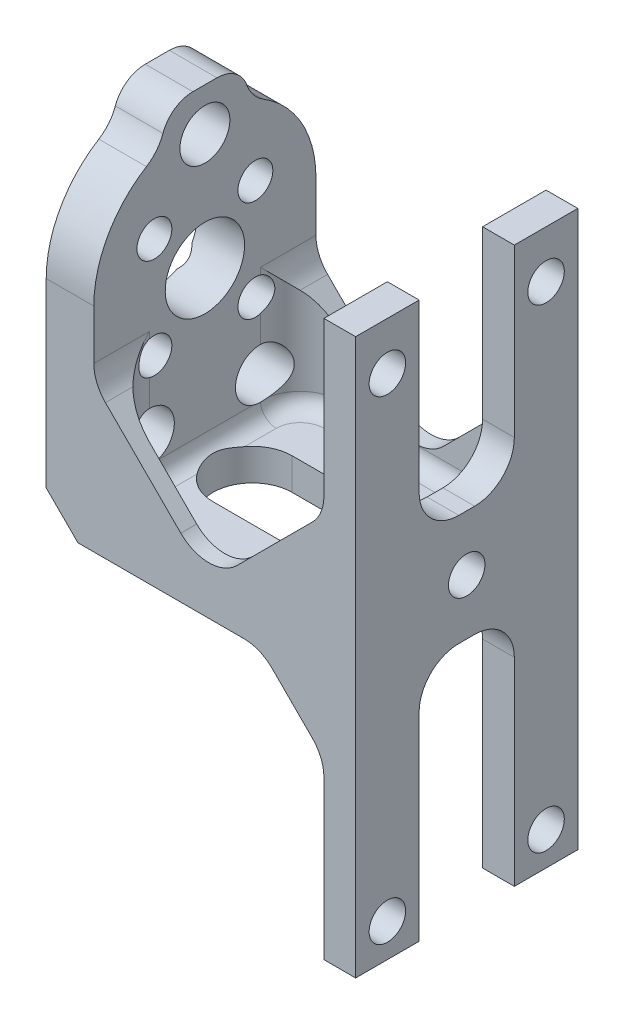
SolidWorks part; units mm, degrees
ref_plane "Front Plane" through (0, 0, 0) normal (0, 0, 1) x (1, 0, 0)
ref_plane "Top Plane" through (0, 0, 0) normal (0, 1, 0) x (1, 0, 0)
ref_plane "Right Plane" through (0, 0, 0) normal (1, 0, 0) x (0, 0, -1)
sketch "Sketch1" plane through (0, 0, 0) normal (0, 1, 0) x (1, 0, 0)
  line L0 (-7.25, 7) -> (7.25, -7) construction
  line L1 (-7.25, 7) -> (7.25, 7)
  line L2 (-7.25, 7) -> (-7.25, -7)
  line L3 (-7.25, -7) -> (7.25, -7)
  line L4 (7.25, 7) -> (7.25, -7)
  dimension "D2" = 14.5
  dimension "D1" = 14
extrude "base" add sketch "Sketch1" along normal blind 2
sketch "Sketch3" plane through (0, 0, 7) normal (0, 0, 1) x (1, 0, 0)
  line L0 (-7.25, 2) -> (7.25, 2) construction
  line L1 (-7.25, 0) -> (-10.25, 0)
  line L2 (-7.25, 0) -> (-7.25, 19)
  line L3 (-7.25, 19) -> (-10.25, 19)
  line L4 (-10.25, 0) -> (-10.25, 19)
  dimension "D1" = 3
  dimension "D2" = 17
extrude "motorFlange" add sketch "Sketch3" against normal up to surface (14 mm away) up to face at (0, 1, -7)
hole_wizard "CSK for M2 Flat Head Machine Screw1" positions "Sketch6" profile "Sketch7" countersink size "M2" standard "ANSI Metric"
sketch "Sketch6" plane through (-10.25, 0, 0) normal (-1, 0, 0) x (0, 0, 1)
  line L1 (-3.182, 15.182) -> (3.182, 15.182)
  line L2 (-3.182, 15.182) -> (-3.182, 8.818)
  line L3 (-3.182, 8.818) -> (3.182, 8.818)
  line L4 (3.182, 15.182) -> (3.182, 8.818)
  line L5 (0, 15.182) -> (0, 19)
  line L7 (-7, 19) -> (7, 19) construction
  line L8 (-3.182, 15.182) -> (3.182, 8.818) construction
  point P0 (-3.182, 15.182)
  point P2 (-3.182, 8.818)
  point P4 (3.182, 8.818)
  point P6 (3.182, 15.182)
  point P121 (0, 19)
  point P129 (0, 12)
  dimension "D3" = 7
  dimension "D1" = 9
sketch "Sketch7" plane through (-10.25, 15.182, -3.182) normal (0, 1, 0) x (0, 0, 1)
  line L0 (0, 0) -> (0, 5.8609)
  line L1 (0, 5.8609) -> (1.1, 5.2)
  line L2 (1.1, 5.2) -> (1.1, 1.1)
  line L3 (1.1, 1.1) -> (2.2, 0)
  line L5 (2.2, 0) -> (0, 0)
  line L6 (-1.1, 1.1) -> (-2.2, 0) construction
  line L10 (0, 5.8609) -> (-1.1, 5.2) construction
  line L11 (0, -6.35) -> (0, 107.95) construction
  dimension "Hole Dia." = 2.2
  dimension "Hole Depth" = 5.2
  dimension "Near C'Sink Dia." = 4.4
  dimension "Near C'Sink Angle" = 90
  dimension "Drill Angle" = 118
sketch "Sketch16" plane through (-10.25, 0, 0) normal (-1, 0, 0) x (0, 0, 1)
  line L0 (-3.182, 15.182) -> (3.182, 8.818) construction
  circle A0 centre (0, 12) radius 2.5
  dimension "D1" = 5
extrude "Cut-Extrude1" cut sketch "Sketch16" against normal blind 10
sketch "Sketch17" plane through (0, 19, 0) normal (0, 1, 0) x (1, 0, 0)
  line L0 (-7.25, 7) -> (-7.25, -7) construction
  line L1 (-10.25, 7) -> (-10.25, -7) construction
  line L2 (-7.25, -2.5) -> (-10.25, -2.5)
  line L3 (-7.25, -2.5) -> (-7.25, 2.5)
  line L4 (-7.25, 2.5) -> (-10.25, 2.5)
  line L5 (-10.25, -2.5) -> (-10.25, 2.5)
  point P8 (-7.25, 0)
  dimension "D1" = 5
extrude "Boss-Extrude5" add sketch "Sketch17" along normal blind 3
sketch "Sketch18" plane through (0, 2, 0) normal (0, 1, 0) x (1, 0, 0)
  line L0 (-7.25, 7) -> (-7.25, -7) construction
  line L1 (-7.25, 2.5) -> (-2.25, 2.5)
  line L2 (-7.25, 2.5) -> (-7.25, -2.5)
  line L3 (-7.25, -2.5) -> (-2.25, -2.5)
  line L4 (-2.25, 2.5) -> (-2.25, -2.5)
  point P6 (-7.25, 0)
  dimension "D1" = 5
  dimension "D2" = 5
extrude "Cut-Extrude2" [suppressed] cut sketch "Sketch18" against normal through all both and the other way through all
sketch "Sketch23" plane through (0, 0, 7) normal (0, 0, 1) x (1, 0, 0)
  line L0 (-10.25, 0) -> (10.554, -20.804) construction
  line L1 (-10.25, 0) -> (7.25, 0) construction
  dimension "D1" = 45
sketch "Sketch4" plane through (0, 0, 7) normal (0, 0, 1) x (1, 0, 0)
  line L1 (7.25, 0) -> (9.25, 0)
  line L2 (7.25, 0) -> (7.25, 7)
  line L3 (7.25, 7) -> (9.25, 7)
  line L4 (9.25, 0) -> (9.25, 7)
  line L5 (-7.25, 2) -> (7.25, 2) construction
  dimension "D1" = 2
  dimension "D2" = 5
extrude "Boss-Extrude3" add sketch "Sketch4" against normal up to surface (14 mm away) up to face at (-3.4167, 7, -7)
sketch "Sketch13" plane through (0, 7, 0) normal (0, 1, 0) x (1, 0, 0)
  line L0 (7.25, 7) -> (7.25, -7) construction
  line L1 (9.25, -7) -> (7.25, -7)
  line L2 (9.25, -7) -> (9.25, -3)
  line L3 (9.25, -3) -> (7.25, -3)
  line L4 (7.25, -7) -> (7.25, -3)
  dimension "D1" = 4
extrude "Boss-Extrude4" add sketch "Sketch13" along normal blind 13
mirror "Mirror5" about plane through (0, 0, 0) normal (0, 0, 1) of "Boss-Extrude4"
sketch "Sketch22" plane through (0, 0, 0) normal (0, -1, 0) x (1, 0, 0)
  line L1 (9.25, 7) -> (7.25, 7)
  line L2 (9.25, 7) -> (9.25, 3)
  line L3 (9.25, 3) -> (7.25, 3)
  line L4 (7.25, 7) -> (7.25, 3)
  line L5 (9.25, -7) -> (7.25, -7)
  line L6 (9.25, -7) -> (9.25, -3)
  line L7 (9.25, -3) -> (7.25, -3)
  line L8 (7.25, -7) -> (7.25, -3)
extrude "Boss-Extrude6" add sketch "Sketch22" along normal blind 15
sketch "Sketch26" plane through (0, 0, 7) normal (0, 0, 1) x (1, 0, 0)
  line L0 (-7.25, 9.25) -> (0, 2)
  line L1 (-7.25, 2) -> (-7.25, 19) construction
  line L2 (-7.25, 2) -> (7.25, 2) construction
  dimension "D1" = 45
rib "Rib3" sketch "Sketch26" sketch "Sketch26" thickness 1 extrusion direction parallel to sketch draft on no parameters "D1"=1
sketch "Sketch27" plane through (0, 0, 7) normal (0, 0, 1) x (1, 0, 0)
  line L0 (0, 2) -> (7.25, 9.25)
  line L1 (7.25, 20) -> (7.25, 2) construction
rib "Rib4" sketch "Sketch27" sketch "Sketch27" thickness 1 extrusion direction parallel to sketch draft on no parameters "D1"=1
sketch "Sketch28" plane through (0, 0, 7) normal (0, 0, 1) x (1, 0, 0)
  line L0 (3.25, 0) -> (7.25, -4)
  line L1 (-10.25, 0) -> (7.25, 0) construction
  line L2 (7.25, -15) -> (7.25, 0) construction
  dimension "D1" = 45
  dimension "D2" = 4
rib "Rib7" sketch "Sketch28" sketch "Sketch28" thickness 1 extrusion direction parallel to sketch draft on no parameters "D1"=1
mirror "Mirror7" about plane through (0, 0, 0) normal (0, 0, 1) of "Rib7", "Rib4", "Rib3"
fillet "Fillet5" radius 2.5 2 edges at (-8.75, 19, 2.5) (-8.75, 19, -2.5)
fillet "Fillet1" radius 7 2 edges at (-8.75, 19, -7) (-8.75, 19, 7)
fillet "Fillet6" radius 2 2 edges at (-8.75, 22, 2.5) (-8.75, 22, -2.5)
fillet "Fillet4" radius 2.5 2 edges at (8.25, 7, -3) (8.25, 7, 3)
fillet "Fillet8" radius 2.5 8 edges at (8.25, 0, -3) (8.25, 0, 3) (7.25, -4, -6.5) (3.25, 0, -6.5) (7.25, -4, 6.5) (3.25, 0, 6.5) (7.25, -2, 6) (7.25, -2, -6)
fillet "Fillet7" radius 1 6 edges at (7.25, 0, -2) (7.25, 0, 2) (3.4822, 0, -6) (3.4822, 0, 6) (6.5178, 0, 5.2678) (6.5178, 0, -5.2678)
fillet "Fillet13" radius 2.5 10 edges at (0, 2, 6.5) (-7.25, 9.25, 6.5) (-7.25, 5.625, 6) (-7.25, 5.625, -6) (7.25, 5.625, -6) (7.25, 5.625, 6) (7.25, 9.25, 6.5) (7.25, 9.25, -6.5) (-7.25, 9.25, -6.5) (0, 2, -6.5)
fillet "Fillet11" radius 1 10 edges at (7.25, 2, 0) (-7.25, 2, 0) (-6.5178, 2, 5.2678) (-6.5178, 2, -5.2678) (-2.375, 2, 6) (2.375, 2, 6) (2.375, 2, -6) (-2.375, 2, -6) (6.5178, 2, -5.2678) (6.5178, 2, 5.2678)
sketch "Sketch21" plane through (0, 2, 0) normal (0, 1, 0) x (1, 0, 0)
  line L1 (-7.25, -3.5) -> (-7.25, 3.5) construction
  circle A0 centre (-3.75, 0) radius 2.5
  point P5 (-7.25, 0)
  point P6 (-6.25, 0)
  dimension "D1" = 5
  dimension "D2" = 1
extrude "wireHole" [suppressed] cut sketch "Sketch21" against normal through all both and the other way through all
sketch "Sketch25" plane through (0, 2, 0) normal (0, 1, 0) x (1, 0, 0)
  line L0 (-4.25, 0) -> (0.75, 0) construction
  line L1 (-4.25, 2.5) -> (0.75, 2.5)
  line L2 (-4.25, -2.5) -> (0.75, -2.5)
  line L3 (-7.25, -3.5) -> (-7.25, 3.5) construction
  arc A0 (-4.25, 2.5) -> (-4.25, -2.5) centre (-4.25, 0) ccw
  arc A1 (0.75, -2.5) -> (0.75, 2.5) centre (0.75, 0) ccw
  point P3 (-1.75, 0)
  point P8 (-6.75, 0)
  point P13 (-7.25, 0)
  dimension "D2" = 5
  dimension "D3" = 2.5
  dimension "D1" = 0.5
extrude "wireSlot" cut sketch "Sketch25" against normal through all both and the other way through all
chamfer "Chamfer1" distance 2 angle 45 1 edges at (-10.25, 0, 0)
hole_wizard "Tapped Hole for M2.2x0.45 Helicoil1" positions "Sketch14" profile "Sketch15" tap size "M2.2x0.45" standard "Helicoil® Metric"
sketch "Sketch14" plane through (9.25, 0, 0) normal (1, 0, 0) x (0, 0, -1)
  line L0 (-5, 20) -> (-5, 17) construction
  line L1 (-7, 20) -> (-3, 20) construction
  line L3 (0, 7) -> (0, 0) construction
  line L6 (0.5, 0) -> (-0.5, 0) construction
  line L7 (-5, 17) -> (-7, 17) construction
  line L8 (-7, -15) -> (-7, 20) construction
  line L16 (-5, -15) -> (-5, -12.9) construction
  line L17 (-3, -15) -> (-7, -15) construction
  line L18 (0.5, 7) -> (-0.5, 7) construction
  point P0 (-5, 17)
  point P41 (0, 3.5)
  point P42 (5, 17)
  point P54 (-5, -12.9)
  point P60 (5, -12.9)
  point P72 (-5, 15.0837)
  dimension "D1" = 32
  dimension "D2" = 2.1
sketch "Sketch15" plane through (9.25, 17, 5) normal (0, 1, 0) x (0, 0, -1)
  line L0 (0, 0) -> (0, 6.691)
  line L1 (0, 6.691) -> (1.15, 6)
  line L2 (1.15, 6) -> (1.15, 0)
  line L5 (1.15, 0) -> (0, 0)
  line L10 (0, 6.691) -> (-1.15, 6) construction
  line L11 (0, -6.35) -> (0, 107.95) construction
  dimension "Tap Drill Dia." = 2.3
  dimension "Tap Drill Depth" = 6
  dimension "Drill Angle" = 118
cosmetic thread "Hole Thread7" parameters "D1"=2, "D2"=2.845
cosmetic thread "Hole Thread8" parameters "D1"=2.7, "D2"=2.845
cosmetic thread "Hole Thread9" parameters "D1"=2.7, "D2"=2.845
cosmetic thread "Hole Thread11" parameters "D1"=2.7, "D2"=2.845
cosmetic thread "Hole Thread12" parameters "D1"=2.7, "D2"=2.845
hole_wizard "Tapped Hole for M3x0.5 Helicoil1" positions "Sketch11" profile "Sketch12" tap size "M3x0.5" standard "Helicoil® Metric"
sketch "Sketch11" plane through (-10.25, 0, 0) normal (-1, 0, 0) x (0, 0, 1)
  line L0 (0, 0) -> (0, 19.2948) construction
  line L1 (-7, 0) -> (7, 0) construction
  line L2 (1.8358, 16.922) -> (0, 19.2948) construction
  line L4 (3.0416, 17.855) -> (0.6299, 15.9891) construction
  arc A0 (2.1803, 13.2233) -> (1.2233, 14.1803) centre (3.182, 15.182) ccw construction
  point P0 (3.5, 4.5)
  point P4 (0, 19.2948)
  point P16 (-3.5, 4.5)
  point P33 (1.8358, 16.922)
  dimension "D1" = 7
  dimension "D2" = 3
  dimension "D3" = 4.5
cosmetic thread "Hole Thread2" parameters "D1"=3.5, "D2"=3.716
cosmetic thread "Hole Thread3" parameters "D1"=3.5, "D2"=3.716
sketch "Sketch12" plane through (-10.25, 4.5, 3.5) normal (0, 1, 0) x (0, 0, 1)
  line L0 (0, 0) -> (0, 8.4464)
  line L1 (0, 8.4464) -> (1.575, 7.5)
  line L2 (1.575, 7.5) -> (1.575, 0)
  line L5 (1.575, 0) -> (0, 0)
  line L10 (0, 8.4464) -> (-1.575, 7.5) construction
  line L11 (0, -6.35) -> (0, 107.95) construction
  dimension "Tap Drill Dia." = 3.15
  dimension "Tap Drill Depth" = 7.5
  dimension "Drill Angle" = 118
cosmetic thread "Hole Thread10" parameters "D1"=3, "D2"=3.716
sketch "Sketch29" plane through (0, 20, 0) normal (0, 1, 0) x (1, 0, 0)
  line L4 (9.25, -7) -> (9.25, -3)
  line L5 (9.25, -3) -> (7.25, -3)
  line L6 (7.25, -3) -> (7.25, -7)
  line L7 (7.25, -7) -> (9.25, -7)
  line L8 (9.25, -7) -> (9.25, -3)
  line L9 (9.25, -3) -> (7.25, -3)
  line L10 (7.25, -3) -> (7.25, -7)
  line L11 (7.25, -7) -> (9.25, -7)
  line L12 (9.25, 7) -> (7.25, 7)
  line L13 (7.25, 7) -> (7.25, 3)
  line L14 (7.25, 3) -> (9.25, 3)
  line L15 (9.25, 3) -> (9.25, 7)
  line L16 (9.25, 7) -> (7.25, 7)
  line L17 (7.25, 7) -> (7.25, 3)
  line L18 (7.25, 3) -> (9.25, 3)
  line L19 (9.25, 3) -> (9.25, 7)
  dimension "D1" = 0
  dimension "D2" = 0
extrude "Boss-Extrude7" [suppressed] add sketch "Sketch29" along normal blind 20
equation "\"motorDiameter\"= 14mm"
equation "\"baseThickness\"= 2mm"
equation "\"motorWallThickness\"= 3mm"
equation "\"boardWallThickness\"= \"baseThickness\""
equation "\"D1@base\" = \"baseThickness\""
equation "\"motorLength\"= 12.5mm"
equation "\"magnetHeight\"= 2mm"
equation "\"rotorClearance\"= 3mm"
equation "\"D1@Sketch3\"=\"motorWallThickness\""
equation "\"D2@Sketch3\"=\"motorDiameter\"+\"rotorClearance\""
equation "\"D1@Sketch4\"=\"boardWallThickness\""
equation "\"D1@Fillet1\"=\"motorDiameter\"/2"
equation "\"D3@Sketch6\"=\"motorDiameter\"/2"
equation "\"encoderClearance\"= 5mm"
equation "\"D2@Sketch4\"=\"motorDiameter\"/2+\"rotorClearance\"-\"encoderClearance\""
equation "\"cutterOD\"= 5mm"
equation "\"cutterSnubRadius\"= 1mm"
equation "\"D1@Fillet4\"= \"cutterOD\" / 2"
equation "\"D1@Sketch1\"=\"motorDiameter\""
equation "\"encoderClearance_vertical\"= 1mm"
equation "\"encoderHeight\"= 1mm"
equation "\"encoderWidth\"= 2mm"
equation "\"D2@Sketch1\"=\"motorLength\"+\"magnetHeight\"+\"encoderHeight\"+\"encoderClearance_vertical\"-\"boardWallThickness\""
equation "\"D1@Fillet5\"=\"cutterOD\"/2"
equation "\"D1@Fillet8\"=\"cutterOD\"/2"
equation "\"D1@Fillet11\"=\"cutterSnubRadius\""
equation "\"D1@Fillet7\"=\"cutterOD\"/2"
equation "\"D3@Sketch25\"=\"cutterOD\"/2"
equation "\"D1@Fillet7\"=\"cutterSnubRadius\"+0"
equation "\"D1@Fillet13\"=\"cutterOD\"/2"
